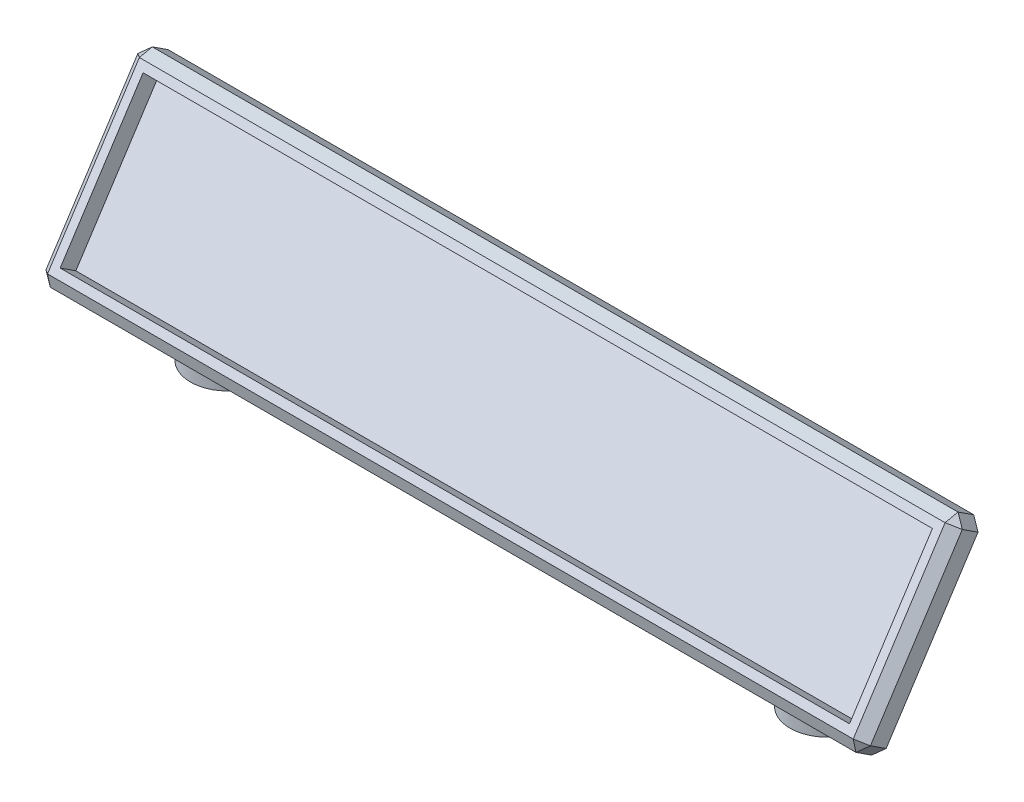
SolidWorks part; units mm, degrees
note: '?' marks a value the reader was unsure of.
ref_plane "Front Plane" through (0, 0, 0) normal (0, 0, 1) x (1, 0, 0)
ref_plane "Top Plane" through (0, 0, 0) normal (0, 1, 0) x (1, 0, 0)
ref_plane "Right Plane" through (0, 0, 0) normal (1, 0, 0) x (0, 0, -1)
sketch "Sketch2" plane through (0, 0, 0) normal (0, 1, 0) x (1, 0, 0)
  line L0 (50.8, 0) -> (-50.8, 0) construction
  circle A0 centre (-50.8, 0) radius 6.35
  circle A1 centre (50.8, 0) radius 6.35
  point P8 (0, 0)
  dimension "D2" = 12.7
  dimension "D1" = 101.6
extrude "Boss-Extrude1" add sketch "Sketch2" along normal blind 19.05
ref_plane "Plane1" through (0, 19.05, 0) normal (0, 1, 0) x (1, 0, 0)
ref_axis "Axis1" through (88.99, 19.05, 0) along (-1, 0, 0)?
ref_plane "Plane2" through (0, 5.6508, 8.7015) normal (0, 0.5446, 0.8387) x (-1, 0, 0)
sketch "Sketch3" plane through (0, 5.6508, 8.7015) normal (0, 0.5446, 0.8387) x (-1, 0, 0)
  line L0 (-50.8, -15.9767) -> (50.8, -15.9767)
  line L2 (-69.85, -31.8517) -> (69.85, -31.8517)
  line L3 (-69.85, -31.8517) -> (-69.85, -0.1017)
  line L4 (-69.85, -0.1017) -> (69.85, -0.1017)
  line L5 (69.85, -31.8517) -> (69.85, -0.1017)
  line L6 (-69.85, -31.8517) -> (69.85, -0.1017) construction
  line L7 (-69.85, -0.1017) -> (69.85, -31.8517) construction
  ellipse E0 centre (50.8, -15.9767) end of major axis (44.45, -15.9767) minor radius 3.4585 construction
  ellipse E1 centre (-50.8, -15.9767) end of major axis (-57.15, -15.9767) minor radius 3.4585 construction
  ellipse E2 centre (50.8, -15.9767) end of major axis (44.45, -15.9767) minor radius 3.4585 construction
  ellipse E3 centre (-50.8, -15.9767) end of major axis (-57.15, -15.9767) minor radius 3.4585 construction
  point P22 (0, -15.9767)
  dimension "D1" = 139.7
  dimension "D2" = 31.75
extrude "Boss-Extrude2" add sketch "Sketch3" along normal blind 6.35
sketch "Sketch8" plane through (0, 19.05, 0) normal (0, 1, 0) x (1, 0, 0)
  line L0 (44.45, 0) -> (57.15, 0) construction
  line L1 (-57.15, 0) -> (-44.45, 0) construction
  line L2 (44.45, 0) -> (57.15, 0)
  line L3 (-57.15, 0) -> (-44.45, 0)
  arc A0 (57.15, 0) -> (44.45, 0) centre (50.8, 0) ccw construction
  arc A1 (-44.45, 0) -> (-57.15, 0) centre (-50.8, 0) ccw construction
  arc A2 (57.15, 0) -> (44.45, 0) centre (50.8, 0) ccw
  arc A3 (-44.45, 0) -> (-57.15, 0) centre (-50.8, 0) ccw
extrude "Boss-Extrude3" add sketch "Sketch8" along normal up to next contours L2 A2 | A3 L3
sketch "Sketch9" plane through (0, 9.1093, 14.0271) normal (0, 0.5446, 0.8387) x (1, 0, 0)
  line L8 (66.875, 28.8767) -> (-66.875, 28.8767)
  line L9 (-66.875, 28.8767) -> (-66.875, 3.0767)
  line L10 (-66.875, 3.0767) -> (66.875, 3.0767)
  line L11 (66.875, 3.0767) -> (66.875, 28.8767)
  line L12 (66.875, 28.8767) -> (-66.875, 28.8767)
  line L13 (-66.875, 28.8767) -> (-66.875, 3.0767)
  line L14 (-66.875, 3.0767) -> (66.875, 3.0767)
  line L15 (66.875, 3.0767) -> (66.875, 28.8767)
  dimension "D1" = 2.975
extrude "Cut-Extrude1" cut sketch "Sketch9" against normal blind 3.175
chamfer "Chamfer2" distance 1.5875 angle 45 12 edges at (-69.85, 19.05, 0) (0, 32.3639, -8.6461) (69.85, 19.05, 0) (0, 5.7361, 8.6461) (0, 9.1946, 13.9717) (-69.85, 7.4653, 11.3089) (-69.85, 22.5085, 5.3256) (69.85, 7.4653, 11.3089) (69.85, 22.5085, 5.3256) (69.85, 34.0931, -5.9834) (0, 35.8224, -3.3206) (-69.85, 34.0931, -5.9834)
hole_wizard "Hole1" positions "3DSketch1" profile "Sketch10" legacy
sketch3d "3DSketch1"
  line L0 (-50.8, 28.8281, 0) -> (-50.8, 0, 0) construction
  line L1 (50.8, 28.8281, 0) -> (50.8, 0, 0) construction
  point P0 (-50.8, 0, 0)
  point P4 (50.8, 0, 0)
sketch "Sketch10" plane through (-50.8, 0, 0) normal (1, 0, 0) x (0, 0, -1)
  line L0 (0, 0) -> (0, 12.7)
  line L1 (0, 12.7) -> (2.8575, 12.7)
  line L2 (2.8575, 12.7) -> (2.8575, 0.6858)
  line L3 (2.8575, 0.6858) -> (3.302, 0.6858)
  line L4 (3.302, 0.6858) -> (3.302, 0)
  line L5 (3.302, 0) -> (0, 0)
  line L6 (0, 110) -> (0, -10) construction
  dimension "Diameter" = 5.715
  dimension "Depth" = 12.7
  dimension "C-Bore Diameter" = 6.604
  dimension "C-Bore Depth" = 0.6858
